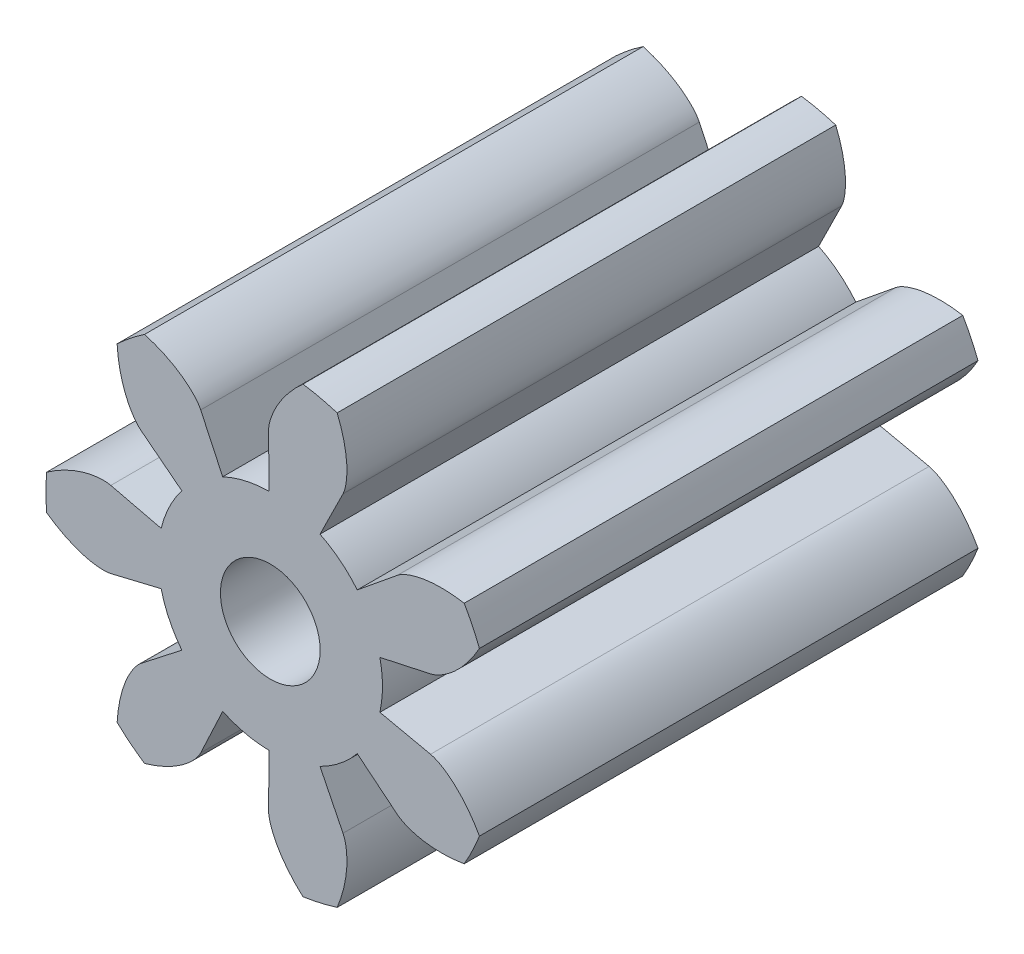
SolidWorks part; units mm, degrees
ref_plane "前视基准面" through (0, 0, 0) normal (0, 0, 1) x (1, 0, 0)
ref_plane "上视基准面" through (0, 0, 0) normal (0, 1, 0) x (1, 0, 0)
ref_plane "右视基准面" through (0, 0, 0) normal (1, 0, 0) x (0, 0, -1)
other "Configuration Table"
sketch "草图1" plane through (0, 0, 0) normal (0, 0, 1) x (1, 0, 0)
  line L0 (0, 0) -> (1.75, 0) construction
  line L1 (0, 0) -> (1.7061, 0.3894) construction
  line L2 (0, 0) -> (1.607, 0.3489)
  line L3 (1.7061, 0.3894) -> (1.7061, -0.3894) construction
  line L4 (0, 0) -> (1.607, -0.3489)
  circle A0 centre (0, 0) radius 2.25
  circle A1 centre (0, 0) radius 1.75 construction
  circle A2 centre (0, 0) radius 1.125
  circle A3 centre (0, 0) radius 1.6445 construction
  circle A4 centre (0, 0) radius 0.5
  spline S0 degree 4 poles (1.607, 0.3489) (1.6193, 0.3515) (1.6529, 0.3616) (1.7136, 0.3906) (1.8045, 0.4507) (1.9091, 0.5461) (2.0246, 0.6863) (2.1338, 0.8693) (2.2237, 1.0852) (2.2875, 1.3292) (2.3207, 1.5789) (2.3254, 1.8308) (2.3028, 2.0941) (2.2408, 2.4154) (2.1185, 2.7866) (1.9144, 3.1926) (1.6216, 3.6033) (1.2716, 3.9672) (0.8779, 4.2809) (0.4443, 4.541) (-0.0123, 4.7475) (-0.4983, 4.8981) (-0.9836, 4.9965) (-1.5014, 5.0378) (-1.8928, 5.0348) (-2.3308, 4.9911) (-2.5782, 4.9493) (-2.8593, 4.8933) (-2.9967, 4.8519) (-3.1191, 4.8203) (-3.1553, 4.8076) (-3.1815, 4.7999) (-3.1956, 4.7958) knots 0 0 0 0 0 0.005604 0.015718 0.02996 0.048734 0.068727 0.096889 0.125051 0.153212 0.181374 0.209535 0.237696 0.271429 0.327752 0.384075 0.440398 0.496721 0.553044 0.609367 0.66569 0.722013 0.778336 0.834659 0.890982 0.909091 0.954545 0.977273 0.988636 0.994318 1 1 1 1 1 construction
  spline S1 degree 4 poles (1.607, 0.3489) (1.6193, 0.3515) (1.6529, 0.3616) (1.7136, 0.3906) (1.8045, 0.4507) (1.9091, 0.5461) (2.0246, 0.6863) (2.1338, 0.8693) (2.2237, 1.0852) (2.2875, 1.3292) (2.3207, 1.5789) (2.3254, 1.8308) (2.3028, 2.0941) (2.2408, 2.4154) (2.1185, 2.7866) (1.9144, 3.1926) (1.6216, 3.6033) (1.2716, 3.9672) (0.8779, 4.2809) (0.4443, 4.541) (-0.0123, 4.7475) (-0.4983, 4.8981) (-0.9836, 4.9965) (-1.5014, 5.0378) (-1.8928, 5.0348) (-2.2178, 5.0024) (-2.3681, 4.9819) (-2.4045, 4.9765) knots 0 0 0 0 0 0.005604 0.015718 0.02996 0.048734 0.068727 0.096889 0.125051 0.153212 0.181374 0.209535 0.237696 0.271429 0.327752 0.384075 0.440398 0.496721 0.553044 0.609367 0.66569 0.722013 0.778336 0.834659 0.890982 0.909091 0.909091 0.909091 0.909091 0.909091
  spline S2 degree 4 poles (1.607, -0.3489) (1.6193, -0.3515) (1.6529, -0.3616) (1.7136, -0.3906) (1.8045, -0.4507) (1.9091, -0.5461) (2.0246, -0.6863) (2.1338, -0.8693) (2.2237, -1.0852) (2.2875, -1.3292) (2.3207, -1.5789) (2.3254, -1.8308) (2.3028, -2.0941) (2.2408, -2.4154) (2.1185, -2.7866) (1.9144, -3.1926) (1.6216, -3.6033) (1.2716, -3.9672) (0.8779, -4.2809) (0.4443, -4.541) (-0.0123, -4.7475) (-0.4983, -4.8981) (-0.9836, -4.9965) (-1.5014, -5.0378) (-1.8928, -5.0348) (-2.3308, -4.9911) (-2.5782, -4.9493) (-2.8593, -4.8933) (-2.9967, -4.8519) (-3.1191, -4.8203) (-3.1553, -4.8076) (-3.1815, -4.7999) (-3.1956, -4.7958) knots 0 0 0 0 0 0.005604 0.015718 0.02996 0.048734 0.068727 0.096889 0.125051 0.153212 0.181374 0.209535 0.237696 0.271429 0.327752 0.384075 0.440398 0.496721 0.553044 0.609367 0.66569 0.722013 0.778336 0.834659 0.890982 0.909091 0.954545 0.977273 0.988636 0.994318 1 1 1 1 1 construction
  spline S3 degree 4 poles (1.607, -0.3489) (1.6193, -0.3515) (1.6529, -0.3616) (1.7136, -0.3906) (1.8045, -0.4507) (1.9091, -0.5461) (2.0246, -0.6863) (2.1338, -0.8693) (2.2237, -1.0852) (2.2875, -1.3292) (2.3207, -1.5789) (2.3254, -1.8308) (2.3028, -2.0941) (2.2408, -2.4154) (2.1185, -2.7866) (1.9144, -3.1926) (1.6216, -3.6033) (1.2716, -3.9672) (0.8779, -4.2809) (0.4443, -4.541) (-0.0123, -4.7475) (-0.4983, -4.8981) (-0.9836, -4.9965) (-1.5014, -5.0378) (-1.8928, -5.0348) (-2.2178, -5.0024) (-2.3681, -4.9819) (-2.4045, -4.9765) knots 0 0 0 0 0 0.005604 0.015718 0.02996 0.048734 0.068727 0.096889 0.125051 0.153212 0.181374 0.209535 0.237696 0.271429 0.327752 0.384075 0.440398 0.496721 0.553044 0.609367 0.66569 0.722013 0.778336 0.834659 0.890982 0.909091 0.909091 0.909091 0.909091 0.909091
  point P15 (1.7061, 0)
  dimension "齿顶圆直径" = 4.5
  dimension "分度圆直径" = 3.5
  dimension "齿根圆直径" = 2.25
  dimension "基圆直径" = 3.2889
  dimension "内孔直径" = 1
  dimension "渐近线镜像线夹角" = 12.857
extrude "凸台-拉伸1" add sketch "草图1" along normal blind 5 contours A0 | A4
extrude "切除-拉伸1" cut sketch "草图1<3>" along normal through all contours A2 S3 A0 S1 region at (1.7817, 0, 0)
sketch "草图1<3>" plane through (0, 0, 0) normal (0, 0, 1) x (1, 0, 0) same geometry as "草图1"
pattern_circular "阵列(圆周)1" count 7 every 51.429 about axis through (0, 0, 5) along (0, 0, 1) of "切除-拉伸1"
equation "\"m\" = 0.5'模数"
equation "\"z\" = 7'齿数"
equation "\"a\"= 20度'压力角"
equation "\"d\"= \"m\" * \"z\"'分度圆直径"
equation "\"da\"= ( \"z\" + 2 ) * \"m\"'齿顶圆直径"
equation "\"df\"= ( \"z\" - 2.5 ) * \"m\"'齿根圆直径"
equation "\"s\"= 0.5 * PI * \"m\"'分度圆齿厚"
equation "\"r\"= 0.38 * \"m\"'齿根圆角"
equation "\"B\"= 0.3 * \"d\"'齿厚"
equation "\"db\"= \"m\" * \"z\" * cos ( \"a\" )'基圆直径"
equation "\"rb\"= \"db\" / 2'基圆半径"
equation "\"齿顶圆直径@草图1\"= \"da\""
equation "\"分度圆直径@草图1\"= \"d\""
equation "\"齿根圆直径@草图1\"= \"df\""
equation "\"基圆直径@草图1\"= \"db\""
equation "\"渐近线镜像线夹角@草图1\"= 360 / 4 / \"z\""
equation "\"h\"= 5'齿轮厚度"
equation "\"ir\"= 1'内孔直径"
equation "\"内孔直径@草图1\"= \"ir\""
equation "\"齿轮厚@凸台-拉伸1\"= \"h\""
equation "\"齿轮夹角@阵列(圆周)1\"= 360 / \"z\""
equation "\"齿数@阵列(圆周)1\"= \"z\""
